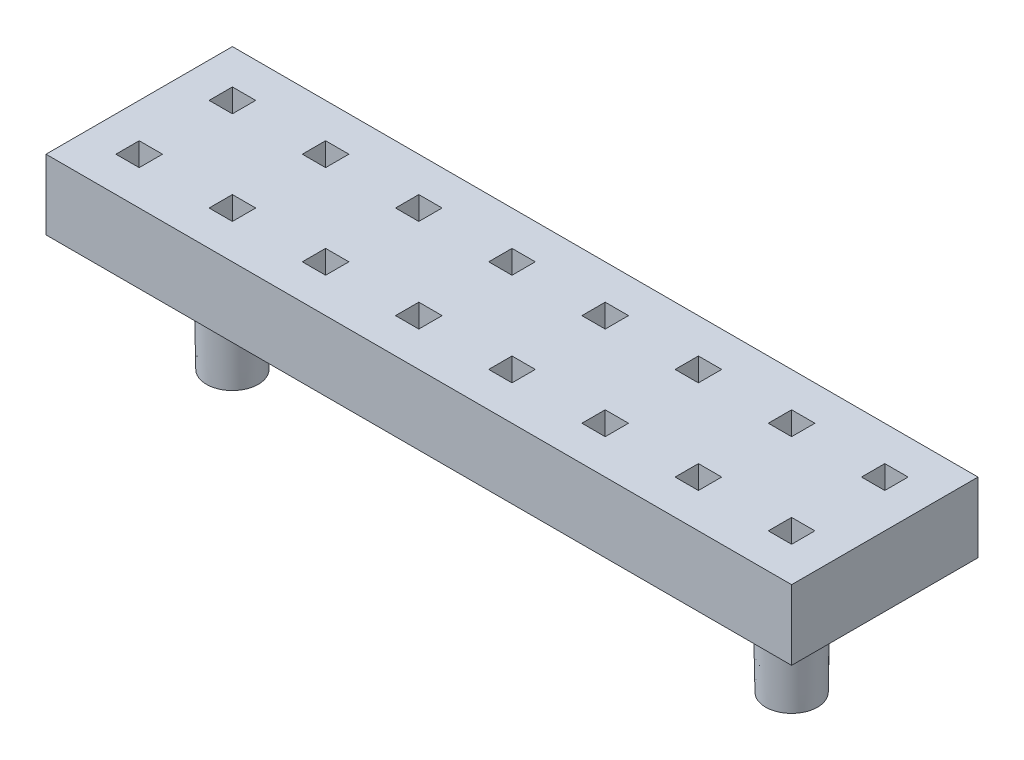
SolidWorks part; units mm, degrees
ref_plane "Front Plane" through (0, 0, 0) normal (0, 0, 1) x (1, 0, 0)
ref_plane "Top Plane" through (0, 0, 0) normal (0, 1, 0) x (1, 0, 0)
ref_plane "Right Plane" through (0, 0, 0) normal (1, 0, 0) x (0, 0, -1)
sketch "Sketch1" plane through (0, 0, 0) normal (0, 1, 0) x (1, 0, 0)
  line L1 (0, 0) -> (16, 0)
  line L2 (0, 0) -> (0, 4)
  line L3 (0, 4) -> (16, 4)
  line L4 (16, 0) -> (16, 4)
extrude "Boss-Extrude1" add sketch "Sketch1" along normal blind 1.5
sketch "Sketch2" plane through (0, 1.5, 0) normal (0, 1, 0) x (1, 0, 0)
  line L0 (2.75, 3.25) -> (3.25, 3.25)
  line L1 (0.75, 3.25) -> (1.25, 3.25)
  line L2 (0.75, 3.25) -> (0.75, 2.75)
  line L3 (0.75, 2.75) -> (1.25, 2.75)
  line L4 (1.25, 3.25) -> (1.25, 2.75)
  line L5 (2.75, 3.25) -> (2.75, 2.75)
  line L6 (2.75, 2.75) -> (3.25, 2.75)
  line L7 (3.25, 3.25) -> (3.25, 2.75)
  line L8 (4.75, 3.25) -> (5.25, 3.25)
  line L9 (4.75, 3.25) -> (4.75, 2.75)
  line L10 (4.75, 2.75) -> (5.25, 2.75)
  line L11 (5.25, 3.25) -> (5.25, 2.75)
  line L12 (6.75, 3.25) -> (7.25, 3.25)
  line L13 (6.75, 3.25) -> (6.75, 2.75)
  line L14 (6.75, 2.75) -> (7.25, 2.75)
  line L15 (7.25, 3.25) -> (7.25, 2.75)
  line L16 (8.75, 3.25) -> (9.25, 3.25)
  line L17 (8.75, 3.25) -> (8.75, 2.75)
  line L18 (8.75, 2.75) -> (9.25, 2.75)
  line L19 (9.25, 3.25) -> (9.25, 2.75)
  line L20 (10.75, 3.25) -> (11.25, 3.25)
  line L21 (10.75, 3.25) -> (10.75, 2.75)
  line L22 (10.75, 2.75) -> (11.25, 2.75)
  line L23 (11.25, 3.25) -> (11.25, 2.75)
  line L24 (12.75, 3.25) -> (13.25, 3.25)
  line L25 (12.75, 3.25) -> (12.75, 2.75)
  line L26 (12.75, 2.75) -> (13.25, 2.75)
  line L27 (13.25, 3.25) -> (13.25, 2.75)
  line L28 (14.75, 3.25) -> (15.25, 3.25)
  line L29 (14.75, 3.25) -> (14.75, 2.75)
  line L30 (14.75, 2.75) -> (15.25, 2.75)
  line L31 (15.25, 3.25) -> (15.25, 2.75)
  line L32 (16.75, 3.25) -> (17.25, 3.25)
  line L33 (16.75, 3.25) -> (16.75, 2.75)
  line L34 (16.75, 2.75) -> (17.25, 2.75)
  line L35 (17.25, 3.25) -> (17.25, 2.75)
  line L36 (18.75, 3.25) -> (19.25, 3.25)
  line L37 (18.75, 3.25) -> (18.75, 2.75)
  line L38 (18.75, 2.75) -> (19.25, 2.75)
  line L39 (19.25, 3.25) -> (19.25, 2.75)
  line L40 (20.75, 3.25) -> (21.25, 3.25)
  line L41 (20.75, 3.25) -> (20.75, 2.75)
  line L42 (20.75, 2.75) -> (21.25, 2.75)
  line L43 (21.25, 3.25) -> (21.25, 2.75)
  line L44 (22.75, 3.25) -> (23.25, 3.25)
  line L45 (22.75, 3.25) -> (22.75, 2.75)
  line L46 (22.75, 2.75) -> (23.25, 2.75)
  line L47 (23.25, 3.25) -> (23.25, 2.75)
  line L48 (24.75, 3.25) -> (25.25, 3.25)
  line L49 (24.75, 3.25) -> (24.75, 2.75)
  line L50 (24.75, 2.75) -> (25.25, 2.75)
  line L51 (25.25, 3.25) -> (25.25, 2.75)
  line L52 (26.75, 3.25) -> (27.25, 3.25)
  line L53 (26.75, 3.25) -> (26.75, 2.75)
  line L54 (26.75, 2.75) -> (27.25, 2.75)
  line L55 (27.25, 3.25) -> (27.25, 2.75)
  line L56 (28.75, 3.25) -> (29.25, 3.25)
  line L57 (28.75, 3.25) -> (28.75, 2.75)
  line L58 (28.75, 2.75) -> (29.25, 2.75)
  line L59 (29.25, 3.25) -> (29.25, 2.75)
  line L60 (30.75, 3.25) -> (31.25, 3.25)
  line L61 (30.75, 3.25) -> (30.75, 2.75)
  line L62 (30.75, 2.75) -> (31.25, 2.75)
  line L63 (31.25, 3.25) -> (31.25, 2.75)
  line L64 (32.75, 3.25) -> (33.25, 3.25)
  line L65 (32.75, 3.25) -> (32.75, 2.75)
  line L66 (32.75, 2.75) -> (33.25, 2.75)
  line L67 (33.25, 3.25) -> (33.25, 2.75)
  line L68 (34.75, 3.25) -> (35.25, 3.25)
  line L69 (34.75, 3.25) -> (34.75, 2.75)
  line L70 (34.75, 2.75) -> (35.25, 2.75)
  line L71 (35.25, 3.25) -> (35.25, 2.75)
  line L72 (0.75, 1.25) -> (1.25, 1.25)
  line L73 (0.75, 1.25) -> (0.75, 0.75)
  line L74 (0.75, 0.75) -> (1.25, 0.75)
  line L75 (1.25, 1.25) -> (1.25, 0.75)
  line L76 (2.75, 1.25) -> (3.25, 1.25)
  line L77 (2.75, 1.25) -> (2.75, 0.75)
  line L78 (2.75, 0.75) -> (3.25, 0.75)
  line L79 (3.25, 1.25) -> (3.25, 0.75)
  line L80 (4.75, 1.25) -> (5.25, 1.25)
  line L81 (4.75, 1.25) -> (4.75, 0.75)
  line L82 (4.75, 0.75) -> (5.25, 0.75)
  line L83 (5.25, 1.25) -> (5.25, 0.75)
  line L84 (6.75, 1.25) -> (7.25, 1.25)
  line L85 (6.75, 1.25) -> (6.75, 0.75)
  line L86 (6.75, 0.75) -> (7.25, 0.75)
  line L87 (7.25, 1.25) -> (7.25, 0.75)
  line L88 (8.75, 1.25) -> (9.25, 1.25)
  line L89 (8.75, 1.25) -> (8.75, 0.75)
  line L90 (8.75, 0.75) -> (9.25, 0.75)
  line L91 (9.25, 1.25) -> (9.25, 0.75)
  line L92 (10.75, 1.25) -> (11.25, 1.25)
  line L93 (10.75, 1.25) -> (10.75, 0.75)
  line L94 (10.75, 0.75) -> (11.25, 0.75)
  line L95 (11.25, 1.25) -> (11.25, 0.75)
  line L96 (12.75, 1.25) -> (13.25, 1.25)
  line L97 (12.75, 1.25) -> (12.75, 0.75)
  line L98 (12.75, 0.75) -> (13.25, 0.75)
  line L99 (13.25, 1.25) -> (13.25, 0.75)
  line L100 (14.75, 1.25) -> (15.25, 1.25)
  line L101 (14.75, 1.25) -> (14.75, 0.75)
  line L102 (14.75, 0.75) -> (15.25, 0.75)
  line L103 (15.25, 1.25) -> (15.25, 0.75)
  line L104 (16.75, 1.25) -> (17.25, 1.25)
  line L105 (16.75, 1.25) -> (16.75, 0.75)
  line L106 (16.75, 0.75) -> (17.25, 0.75)
  line L107 (17.25, 1.25) -> (17.25, 0.75)
  line L108 (18.75, 1.25) -> (19.25, 1.25)
  line L109 (18.75, 1.25) -> (18.75, 0.75)
  line L110 (18.75, 0.75) -> (19.25, 0.75)
  line L111 (19.25, 1.25) -> (19.25, 0.75)
  line L112 (20.75, 1.25) -> (21.25, 1.25)
  line L113 (20.75, 1.25) -> (20.75, 0.75)
  line L114 (20.75, 0.75) -> (21.25, 0.75)
  line L115 (21.25, 1.25) -> (21.25, 0.75)
  line L116 (22.75, 1.25) -> (23.25, 1.25)
  line L117 (22.75, 1.25) -> (22.75, 0.75)
  line L118 (22.75, 0.75) -> (23.25, 0.75)
  line L119 (23.25, 1.25) -> (23.25, 0.75)
  line L120 (24.75, 1.25) -> (25.25, 1.25)
  line L121 (24.75, 1.25) -> (24.75, 0.75)
  line L122 (24.75, 0.75) -> (25.25, 0.75)
  line L123 (25.25, 1.25) -> (25.25, 0.75)
  line L124 (26.75, 1.25) -> (27.25, 1.25)
  line L125 (26.75, 1.25) -> (26.75, 0.75)
  line L126 (26.75, 0.75) -> (27.25, 0.75)
  line L127 (27.25, 1.25) -> (27.25, 0.75)
  line L128 (28.75, 1.25) -> (29.25, 1.25)
  line L129 (28.75, 1.25) -> (28.75, 0.75)
  line L130 (28.75, 0.75) -> (29.25, 0.75)
  line L131 (29.25, 1.25) -> (29.25, 0.75)
  line L132 (30.75, 1.25) -> (31.25, 1.25)
  line L133 (30.75, 1.25) -> (30.75, 0.75)
  line L134 (30.75, 0.75) -> (31.25, 0.75)
  line L135 (31.25, 1.25) -> (31.25, 0.75)
  line L136 (32.75, 1.25) -> (33.25, 1.25)
  line L137 (32.75, 1.25) -> (32.75, 0.75)
  line L138 (32.75, 0.75) -> (33.25, 0.75)
  line L139 (33.25, 1.25) -> (33.25, 0.75)
  line L140 (34.75, 1.25) -> (35.25, 1.25)
  line L141 (34.75, 1.25) -> (34.75, 0.75)
  line L142 (34.75, 0.75) -> (35.25, 0.75)
  line L143 (35.25, 1.25) -> (35.25, 0.75)
  line L144 (1.25, 3.25) -> (1.25, 4) construction
  line L145 (16, 4) -> (0, 4) construction
  line L146 (1.25, 0.75) -> (1.25, 0) construction
  line L147 (0, 0) -> (16, 0) construction
  dimension "D1" = 18
  dimension "D2" = 2
extrude "Cut-Extrude1" cut sketch "Sketch2" against normal blind 2
sketch "Sketch3" plane through (0, 0, 0) normal (0, 1, 0) x (1, 0, 0)
  line L0 (1.25, 2.75) -> (2.75, 1.25) construction
  line L1 (13.25, 2.75) -> (14.75, 1.25) construction
  line L2 (1.25, 1.25) -> (2.75, 2.75) construction
  line L3 (2.75, 2.75) -> (3.25, 2.75) construction
  line L4 (14.75, 2.75) -> (13.25, 1.25) construction
  circle A0 centre (2, 2) radius 0.6
  circle A1 centre (14, 2) radius 0.6
extrude "Boss-Extrude2" add sketch "Sketch3" against normal blind 2.5 draft 1
ref_axis "Axis1" through (2, 3.1857, -2) along (0, -1, 0)
ref_axis "Axis2" through (14, 2.6428, -2) along (0, -1, 0)
